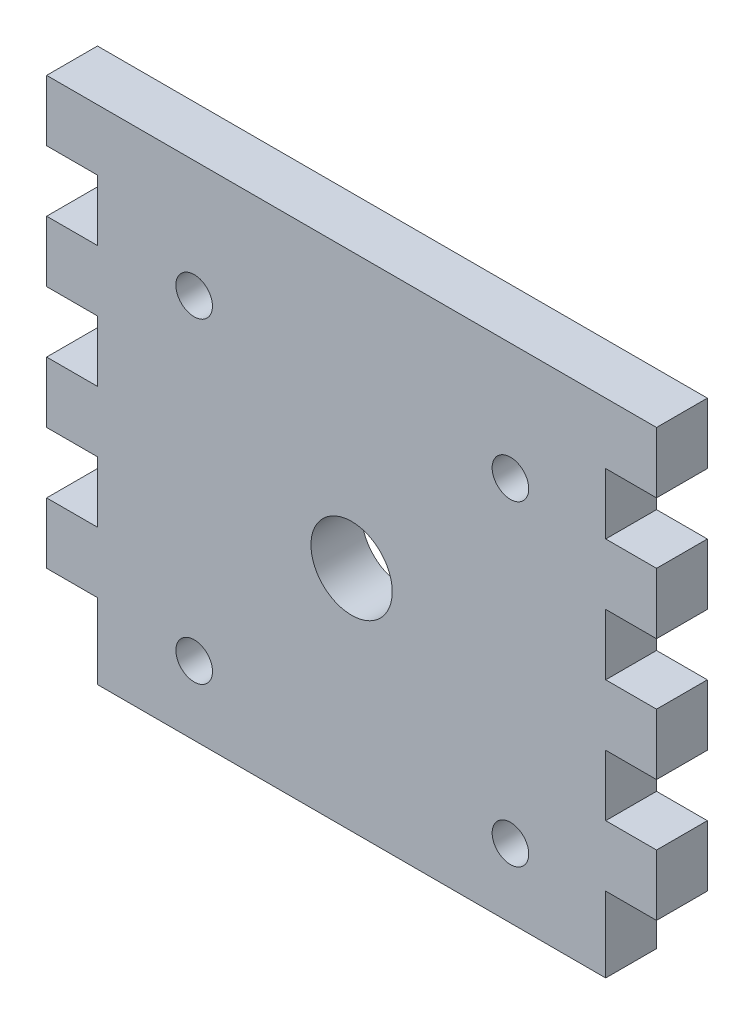
SolidWorks part; units mm, degrees
ref_plane "Front Plane" through (0, 0, 0) normal (0, 0, 1) x (1, 0, 0)
ref_plane "Top Plane" through (0, 0, 0) normal (0, 1, 0) x (1, 0, 0)
ref_plane "Right Plane" through (0, 0, 0) normal (1, 0, 0) x (0, 0, -1)
sketch "Sketch1" plane through (0, 0, 0) normal (0, 0, 1) x (1, 0, 0)
  line L1 (-37.8801, 17.0433) -> (38.3199, 17.0433)
  line L2 (-37.8801, 17.0433) -> (-37.8801, -59.1567)
  line L3 (-37.8801, -59.1567) -> (38.3199, -59.1567)
  line L4 (38.3199, 17.0433) -> (38.3199, -59.1567)
  dimension "D1" = 76.2
  dimension "D2" = 76.2
extrude "Boss-Extrude1" add sketch "Sketch1" along normal blind 6.35
sketch "Sketch2" plane through (0, 0, 6.35) normal (0, 0, 1) x (1, 0, 0)
  line L0 (-37.8801, 17.0433) -> (-31.5301, 17.0433)
  line L1 (38.3199, 17.0433) -> (-37.8801, 17.0433) construction
  line L2 (-31.5301, 17.0433) -> (-31.5301, 9.4233)
  line L3 (-31.5301, 9.4233) -> (-37.8801, 9.4233)
  line L4 (-37.8801, 17.0433) -> (-37.8801, -59.1567) construction
  line L5 (-37.8801, 9.4233) -> (-37.8801, 1.8033)
  line L6 (-37.8801, 1.8033) -> (-31.5301, 1.8033)
  line L7 (-31.5301, 1.8033) -> (-31.5301, -5.8167)
  line L8 (-31.5301, -5.8167) -> (-37.8801, -5.8167)
  line L9 (-37.8801, -5.8167) -> (-37.8801, -13.4367)
  line L10 (-37.8801, -13.4367) -> (-31.5301, -13.4367)
  line L11 (-31.5301, -13.4367) -> (-31.5301, -21.0567)
  line L12 (-31.5301, -21.0567) -> (-37.8801, -21.0567)
  line L13 (-37.8801, -21.0567) -> (-46.7258, -21.0567)
  line L14 (-37.8801, -21.0567) -> (-37.8801, -28.6767) [skipped]
  line L15 (-46.7258, -21.0567) -> (-46.7258, 17.0433)
  line L16 (-46.7258, 17.0433) -> (-37.8801, 17.0433)
  line L19 (47.1657, -21.0567) -> (47.1657, 17.0433)
  line L20 (38.3199, -21.0567) -> (47.1657, -21.0567)
  line L21 (31.9699, -21.0567) -> (38.3199, -21.0567)
  line L22 (31.9699, -13.4367) -> (31.9699, -21.0567)
  line L23 (38.3199, -13.4367) -> (31.9699, -13.4367)
  line L24 (38.3199, -5.8167) -> (38.3199, -13.4367)
  line L25 (31.9699, -5.8167) -> (38.3199, -5.8167)
  line L26 (31.9699, 1.8033) -> (31.9699, -5.8167)
  line L27 (38.3199, 1.8033) -> (31.9699, 1.8033)
  line L28 (38.3199, 9.4233) -> (38.3199, 1.8033)
  line L29 (31.9699, 9.4233) -> (38.3199, 9.4233)
  line L30 (31.9699, 17.0433) -> (31.9699, 9.4233)
  line L31 (38.3199, 17.0433) -> (31.9699, 17.0433)
  line L32 (47.1657, 17.0433) -> (38.3199, 17.0433)
  dimension "D1" = 7.62
  dimension "D2" = 7.62
  dimension "D3" = 6.35
  dimension "D4" = 6.35
  dimension "D6" = 38.1
  dimension "D5" = 3
extrude "Cut-Extrude1" cut sketch "Sketch2" against normal blind 6.35
sketch "Sketch3" plane through (0, 0, 6.35) normal (0, 0, 1) x (1, 0, 0)
  line L1 (-31.5301, -21.0567) -> (-37.8801, -21.0567)
  line L2 (-31.5301, -21.0567) -> (-31.5301, -59.1567)
  line L3 (-31.5301, -59.1567) -> (-37.8801, -59.1567)
  line L4 (-37.8801, -21.0567) -> (-37.8801, -59.1567)
  line L5 (31.9699, -21.0567) -> (38.3199, -21.0567)
  line L6 (31.9699, -21.0567) -> (31.9699, -59.1567)
  line L7 (31.9699, -59.1567) -> (38.3199, -59.1567)
  line L8 (38.3199, -21.0567) -> (38.3199, -59.1567)
extrude "Cut-Extrude2" cut sketch "Sketch3" against normal blind 6.35
sketch "Sketch4" plane through (0, 0, 6.35) normal (0, 0, 1) x (1, 0, 0)
  line L0 (-31.5301, -13.4367) -> (-31.5301, -21.0567)
  line L1 (-31.5301, -59.1567) -> (-31.5301, -13.4367) construction
  line L2 (-31.5301, -21.0567) -> (-37.8801, -21.0567)
  line L3 (-37.8801, -21.0567) -> (-37.8801, -28.6767)
  line L4 (-37.8801, -28.6767) -> (-31.5301, -28.6767)
  line L5 (-31.5301, -21.0567) -> (-31.5301, -28.6767)
  line L6 (0.2199, 17.0433) -> (0.2199, -59.1567)
  line L7 (31.9699, 17.0433) -> (-31.5301, 17.0433) construction
  line L8 (-31.5301, -59.1567) -> (31.9699, -59.1567) construction
  line L9 (31.9699, -21.0567) -> (38.3199, -21.0567)
  line L10 (38.3199, -21.0567) -> (38.3199, -28.6767)
  line L11 (38.3199, -28.6767) -> (31.9699, -28.6767)
  line L12 (31.9699, -21.0567) -> (31.9699, -28.6767)
  line M6 (-31.5301, -13.4367) -> (-31.5301, -59.1567)
  line M8 (31.9699, -59.1567) -> (31.9699, -13.4367)
  dimension "D1" = 7.62
  dimension "D2" = 7.62
  dimension "D3" = 6.35
  dimension "D4" = 6.35
extrude "Boss-Extrude3" add sketch "Sketch4" against normal blind 6.35 contours L3 L4 L2 M6 | L11 L10 L9 M8 region at (-34.7051, -24.8667, 6.35) region at (35.1449, -24.8667, 6.35)
sketch "Sketch5" plane through (0, 17.0433, 0) normal (0, 1, 0) x (1, 0, 0)
  line L1 (-31.5301, 0) -> (31.9699, 0)
  line L2 (-31.5301, 0) -> (-31.5301, -6.35)
  line L3 (-31.5301, -6.35) -> (31.9699, -6.35)
  line L4 (31.9699, 0) -> (31.9699, -6.35)
extrude "Cut-Extrude3" cut sketch "Sketch5" against normal blind 7.62
sketch "Sketch6" plane through (0, 0, 6.35) normal (0, 0, 1) x (1, 0, 0)
  line L0 (-31.5301, -59.1567) -> (31.9699, -59.1567) construction
  line L1 (-19.4468, -5.1999) -> (0.2199, -24.8667) construction
  line L2 (0.2199, -24.8667) -> (-37.8801, -24.8667) construction
  line L3 (31.9699, -28.6767) -> (31.9699, -59.1567) construction
  circle A0 centre (0.2199, -24.8667) radius 5.08
  circle A5 centre (-19.4468, -5.1999) radius 2.286
  circle A6 centre (20.0663, -5.1999) radius 2.286
  circle A7 centre (20.0663, -44.7131) radius 2.286
  circle A8 centre (-19.4468, -44.7131) radius 2.286
  point P16 (0.2825, -24.9292)
  point P18 (0.3097, -24.9565)
  dimension "D3" = 10.16
  dimension "D6" = 4
  dimension "D8" = 4.572
  dimension "D1" = 34.29
  dimension "D2" = 31.75
  dimension "D4" = 45
  dimension "D5" = 27.813
extrude "Cut-Extrude4" cut sketch "Sketch6" against normal through all
sketch "Sketch7" plane through (0, 0, 6.35) normal (0, 0, 1) x (1, 0, 0)
  line L0 (-31.5301, -28.6767) -> (-31.5301, -36.2967)
  line L1 (-31.5301, -59.1567) -> (-31.5301, -28.6767) construction
  line L2 (-31.5301, -36.2967) -> (-37.8801, -36.2967)
  line L3 (31.9699, -28.6767) -> (31.9699, -36.2967)
  line L4 (31.9699, -28.6767) -> (31.9699, -59.1567) construction
  line L5 (31.9699, -36.2967) -> (38.3199, -36.2967)
  line L6 (-37.8801, -36.2967) -> (-37.8801, -43.9167)
  line L7 (-37.8801, -43.9167) -> (-31.5301, -43.9167)
  line L8 (38.3199, -36.2967) -> (38.3199, -43.9167)
  line L9 (38.3199, -43.9167) -> (31.9699, -43.9167)
  line L12 (-31.5301, -43.9167) -> (-31.5301, -59.1567)
  line M27 (-31.5301, -28.6767) -> (-31.5301, -59.1567)
  line M29 (31.9699, -59.1567) -> (31.9699, -28.6767)
  dimension "D1" = 7.62
  dimension "D2" = 6.35
  dimension "D3" = 7.62
  dimension "D4" = 6.35
  dimension "D5" = 7.62
  dimension "D6" = 7.62
  dimension "D7" = 6.35
  dimension "D8" = 6.35
extrude "Boss-Extrude4" add sketch "Sketch7" against normal blind 6.35 contours L6 L7 L2 M27 | L9 L8 L5 M29 region at (-34.7051, -40.1067, 6.35) region at (35.1449, -40.1067, 6.35)
sketch "Sketch8" plane through (0, 0, 6.35) normal (0, 0, 1) x (1, 0, 0)
sketch "Sketch9" plane through (0, 0, 6.35) normal (0, 0, 1) x (1, 0, 0)
  line L0 (-31.5301, -43.9167) -> (-31.5301, -59.1567)
  line L1 (-31.5301, -59.1567) -> (31.9699, -59.1567)
  line L2 (31.9699, -59.1567) -> (31.9699, -43.9167)
  line L3 (31.9699, -43.9167) -> (31.9699, -59.1567) construction
  line L6 (-31.5301, -53.3208) -> (31.9699, -53.3208)
  line L7 (-31.5301, -53.3208) -> (-31.5301, -59.1567)
  line L8 (-31.5301, -59.1567) -> (31.9699, -59.1567)
  line L9 (31.9699, -53.3208) -> (31.9699, -59.1567)
  line M28 (-31.5301, -59.1567) -> (31.9699, -59.1567)
  line M29 (31.9699, -59.1567) -> (31.9699, -43.9167)
extrude "Cut-Extrude5" cut sketch "Sketch9" against normal blind 6.35 contours L6 L0 M28 M29 region at (0.2199, -56.2388, 6.35)
